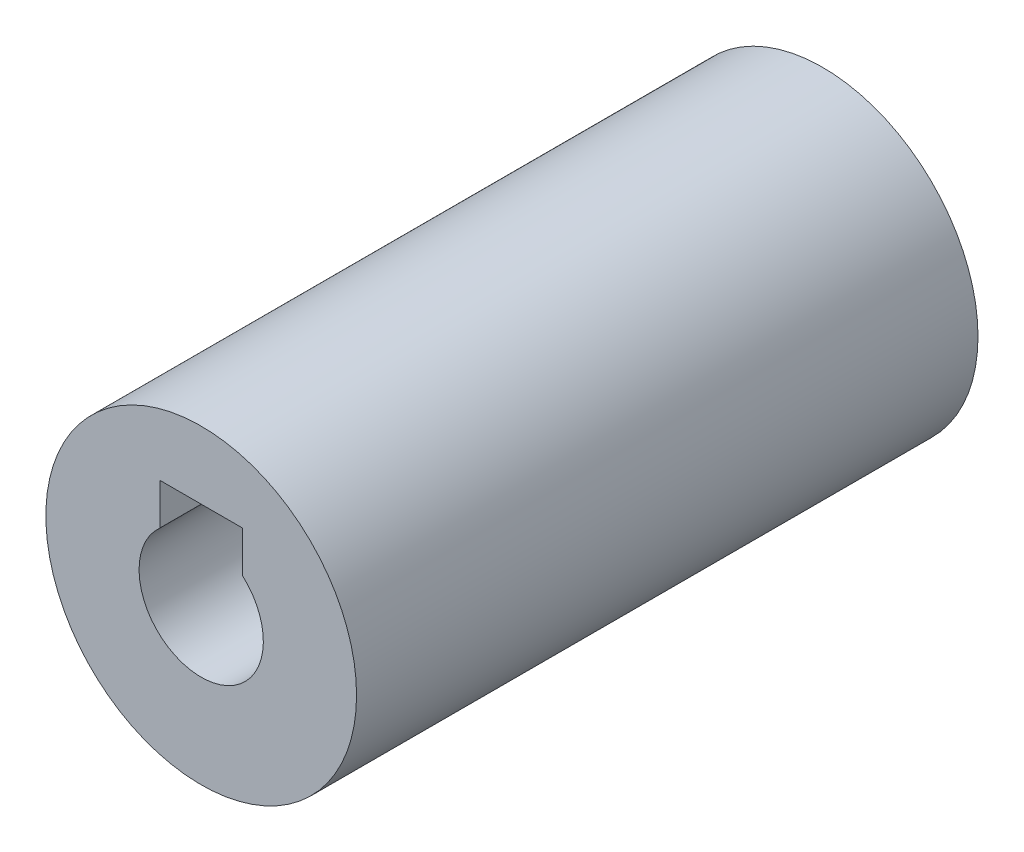
SolidWorks part; units mm, degrees
ref_plane "Front Plane" through (0, 0, 0) normal (0, 0, 1) x (1, 0, 0)
ref_plane "Top Plane" through (0, 0, 0) normal (0, 1, 0) x (1, 0, 0)
ref_plane "Right Plane" through (0, 0, 0) normal (1, 0, 0) x (0, 0, -1)
sketch "Sketch1" plane through (0, 0, 0) normal (0, 0, 1) x (1, 0, 0)
  circle A0 centre (0, 0) radius 3
  circle A1 centre (0, 0) radius 7.5
  dimension "D1" = 15
  dimension "D2" = 6
extrude "Boss-Extrude1" add sketch "Sketch1" along normal blind 30
sketch "Sketch2" plane through (0, 0, 30) normal (0, 0, 1) x (1, 0, 0)
  line L0 (0, 0) -> (0, 6.5951) construction
  line L1 (2, 4.2361) -> (-2, 4.2361)
  line L2 (-2, 4.2361) -> (-2, 2.2361)
  line L3 (2, 4.2361) -> (2, 2.2361)
  circle A0 centre (0, 0) radius 3 construction
  circle A1 centre (0, 0) radius 3
  point P11 (0, 4.2361)
  circle M6 centre (0, 0) radius 3
  dimension "D1" = 4
  dimension "D2" = 2
extrude "Cut-Extrude1" cut sketch "Sketch2" against normal through all contours L0 L1 L2 M6 | L0 A1 L3 L1 region at (-1.0835, 3.4812, 30) region at (1.0835, 3.4812, 30)
